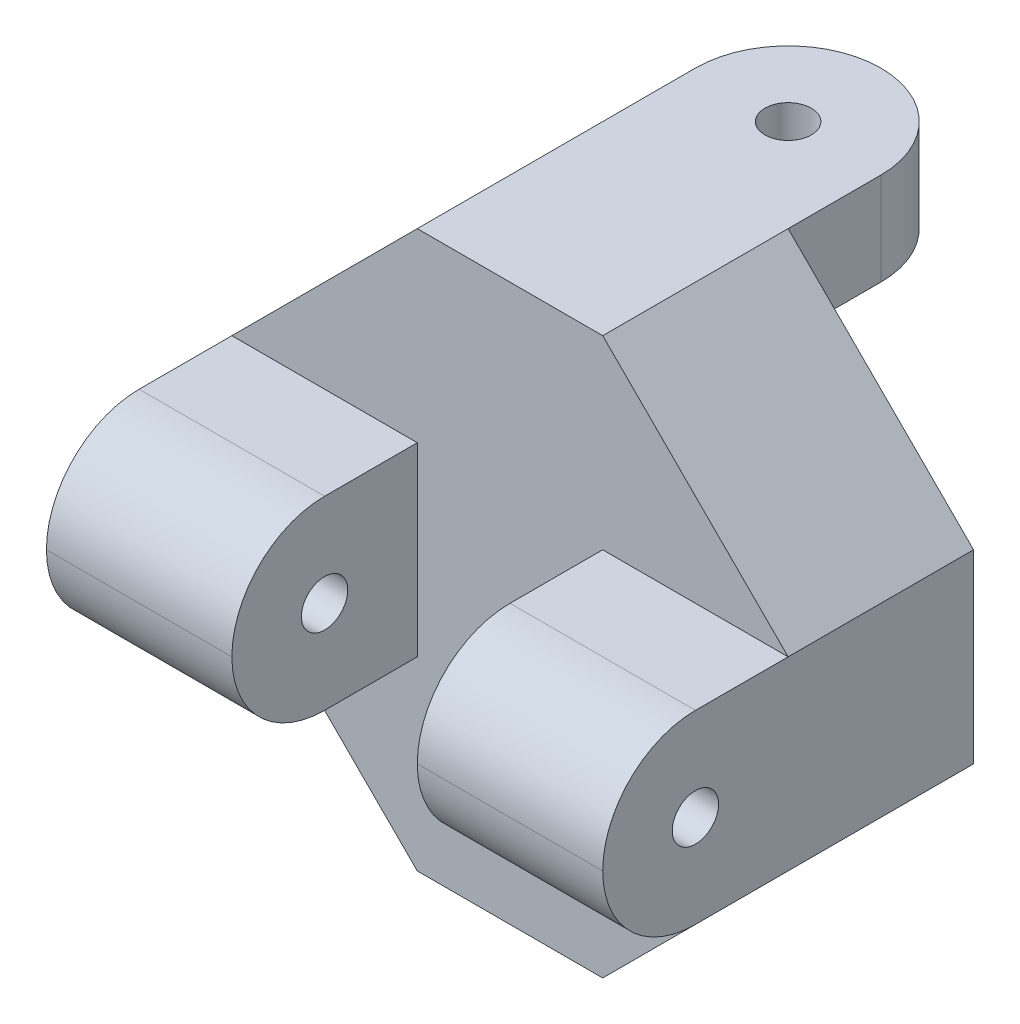
SolidWorks part; units mm, degrees
ref_plane "Front Plane" through (0, 0, 0) normal (0, 0, 1) x (1, 0, 0)
ref_plane "Top Plane" through (0, 0, 0) normal (0, 1, 0) x (1, 0, 0)
ref_plane "Right Plane" through (0, 0, 0) normal (1, 0, 0) x (0, 0, -1)
sketch "Sketch1" plane through (0, 0, 0) normal (0, 0, 1) x (1, 0, 0)
  line L1 (0, 0) -> (25.4, 0)
  line L2 (0, 0) -> (0, 25.4)
  line L3 (0, 25.4) -> (25.4, 25.4)
  line L4 (25.4, 0) -> (25.4, 25.4)
  line L5 (0, 0) -> (25.4, 25.4) construction
  line L6 (0, 25.4) -> (25.4, 0) construction
  line L7 (0, 25.4) -> (-25.4, 25.4)
  line L8 (0, 25.4) -> (0, 0)
  line L9 (0, 0) -> (-25.4, 0)
  line L10 (-25.4, 25.4) -> (-25.4, 0)
  line L11 (0, 25.4) -> (-25.4, 0) construction
  line L12 (0, 0) -> (-25.4, 25.4) construction
  line L13 (25.4, 25.4) -> (50.8, 25.4)
  line L14 (25.4, 25.4) -> (25.4, 0)
  line L15 (25.4, 0) -> (50.8, 0)
  line L16 (50.8, 25.4) -> (50.8, 0)
  line L17 (25.4, 25.4) -> (50.8, 0) construction
  line L18 (25.4, 0) -> (50.8, 25.4) construction
  point P4 (12.7, 12.7)
  point P8 (-12.7, 12.7)
  point P11 (38.1, 12.7)
  dimension "D1" = 76.2
  dimension "D2" = 25.4
  dimension "D3" = 25.4
extrude "Boss-Extrude1" add sketch "Sketch1" along normal mid plane 25.4 contours L7 L10 L9 L2 | L16 L13 L4 L15 region at (-12.7, 12.7, 0) region at (38.1, 12.7, 0)
sketch "Sketch2" plane through (0, 0, -12.7) normal (0, 0, -1) x (-1, 0, 0)
  line L0 (-50.8, 25.4) -> (-25.4, 50.8)
  line L1 (-25.4, 50.8) -> (0, 50.8)
  line L2 (0, 50.8) -> (25.4, 25.4)
  line L3 (25.4, 25.4) -> (25.4, 0)
  line L4 (25.4, 0) -> (0, -25.4)
  line L5 (0, -25.4) -> (-25.4, -25.4)
  line L6 (-25.4, -25.4) -> (-50.8, 0)
  line L7 (-50.8, 0) -> (-50.8, 25.4)
  point P9 (-38.0752, -32.6299)
  point P13 (-19.6243, 43.8757)
extrude "Boss-Extrude2" add sketch "Sketch2" along normal blind 25.4
sketch "Sketch3" plane through (50.8, 0, 0) normal (1, 0, 0) x (0, 0, -1)
  line L3 (-12.7, 0) -> (12.7, 0) construction
  line L4 (-12.7, 25.4) -> (12.7, 25.4) construction
  line L6 (-12.7, 25.4) -> (-12.7, 0) construction
  circle A0 centre (0, 12.7) radius 3.175
  arc A1 (0, 25.4) -> (0, 0) centre (0, 12.7) ccw construction
  point P0 (0, 12.7)
  point P7 (-12.7, 0)
  point P10 (-4.0327, 0)
  point P11 (-1.0294, 25.4)
  point P14 (-12.7, 25.4)
  point P16 (-12.7, 0)
  point P19 (0, 0)
  point P20 (13.8799, 10.0546)
  point P21 (-1.3512, 0)
  point P22 (-0.7076, 12.7)
  dimension "D1" = 6.35
extrude "Cut-Extrude1" cut sketch "Sketch3" against normal through all contours A0
fillet "Fillet1" radius 12.7 4 edges at (38.1, 0, 12.7) (-12.7, 0, 12.7) (-12.7, 25.4, 12.7) (38.1, 25.4, 12.7)
sketch "Sketch4" plane through (0, 50.8, 0) normal (0, 1, 0) x (1, 0, 0)
  line L0 (50.8, 0) -> (50.8, 12.7) construction
  line L1 (0, 38.1) -> (25.4, 38.1)
  line L2 (0, 38.1) -> (0, 50.8)
  line L3 (0, 50.8) -> (25.4, 50.8)
  line L4 (25.4, 38.1) -> (25.4, 50.8)
  line L5 (0, 38.1) -> (25.4, 50.8) construction
  line L6 (0, 50.8) -> (25.4, 38.1) construction
  line L7 (25.4, 38.1) -> (25.4, 12.7) construction
  circle A0 centre (12.7, 50.8) radius 12.7
  circle A1 centre (12.7, 50.8) radius 3.175
  point P4 (12.7, 44.45)
  line M9 (25.4, 38.1) -> (0, 38.1)
  dimension "D1" = 6.35
extrude "Boss-Extrude3" add sketch "Sketch4" against normal up to surface (76.2 mm away) contours A1 L3 A0 | A1 L3 A0 | A0 L2 L1 | A0 L4 M9 region at (2.8368, 50.8, -40.9368) region at (22.5632, 50.8, -40.9368) region at (12.7, 50.8, -45.1405) region at (12.7, 50.8, -56.4595) up to face at (12.7, -25.4, -25.4)
sketch "Sketch5" plane through (25.4, 0, 0) normal (1, 0, 0) x (0, 0, -1)
  line L0 (38.1, -25.4) -> (38.1, 50.8) construction
  line L1 (38.1, -12.7) -> (63.5, -12.7)
  line L2 (38.1, -12.7) -> (38.1, 38.1)
  line L3 (38.1, 38.1) -> (63.5, 38.1)
  line L4 (63.5, -12.7) -> (63.5, 38.1)
  line L5 (38.1, -12.7) -> (63.5, 38.1) construction
  line L6 (38.1, 38.1) -> (63.5, -12.7) construction
  line L7 (63.5, -25.4) -> (63.5, 50.8) construction
  line L12 (38.1, 25.4) -> (38.1, 0) construction
  point P4 (50.8, 12.7)
  point P11 (0, 0)
  point P14 (38.1, 12.7)
  dimension "D1" = 50.8
extrude "Cut-Extrude2" cut sketch "Sketch5" against normal through all
